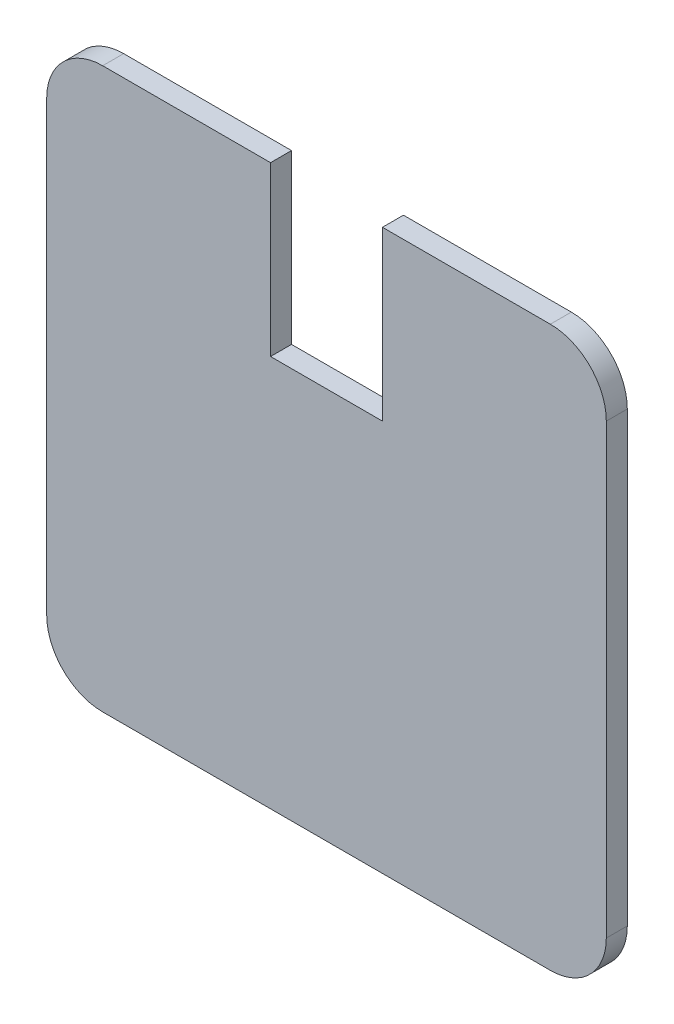
SolidWorks part; units mm, degrees
material "Polyurethane Foam Rigid"
ref_plane "Front Plane" through (0, 0, 0) normal (0, 0, 1) x (1, 0, 0)
ref_plane "Top Plane" through (0, 0, 0) normal (0, 1, 0) x (1, 0, 0)
ref_plane "Right Plane" through (0, 0, 0) normal (1, 0, 0) x (0, 0, -1)
sketch "Sketch1" plane through (0, 0, 0) normal (0, 0, 1) x (1, 0, 0)
  line L2 (-63.5, 50.8) -> (-63.5, -50.8)
  line L3 (-50.8, -63.5) -> (50.8, -63.5)
  line L4 (63.5, 50.8) -> (63.5, -50.8)
  line L5 (-12.7, 63.5) -> (12.7, 63.5) construction
  line L6 (-12.7, 63.5) -> (-12.7, 25.4)
  line L11 (50.8, 63.5) -> (12.7, 63.5)
  line L12 (-12.7, 63.5) -> (-50.8, 63.5)
  line L13 (0, 0) -> (0, 25.4) construction
  line L14 (-12.7, 25.4) -> (12.7, 25.4)
  line L15 (12.7, 25.4) -> (12.7, 63.5)
  line L16 (-59.7803, 59.7803) -> (59.7803, -59.7803) construction
  arc A0 (-63.5, -50.8) -> (-50.8, -63.5) centre (-50.8, -50.8) ccw
  arc A1 (50.8, -63.5) -> (63.5, -50.8) centre (50.8, -50.8) ccw
  arc A2 (63.5, 50.8) -> (50.8, 63.5) centre (50.8, 50.8) ccw
  arc A3 (-50.8, 63.5) -> (-63.5, 50.8) centre (-50.8, 50.8) ccw
  point P0 (0, 0)
  point P1 (0, 0)
  point P21 (59.7803, -59.7803)
  dimension "D3" = 12.7
  dimension "D1" = 127
  dimension "D5" = 25.4
  dimension "D2" = 38.1
  dimension "D4" = 127
extrude "Boss-Extrude1" add sketch "Sketch1" along normal blind 4.7625
equation "\"height\"= 8.875"
equation "\"span\" = 48"
equation "\"wing_chord\"= 9"
equation "\"fuse_len\"= 15"
equation "\"fuse_height\"= 5"
equation "\"fuse_wid\"= 5"
equation "\"D1@Sketch1\"=\"fuse_height\""
equation "\"D4@Sketch1\"=\"fuse_wid\""
